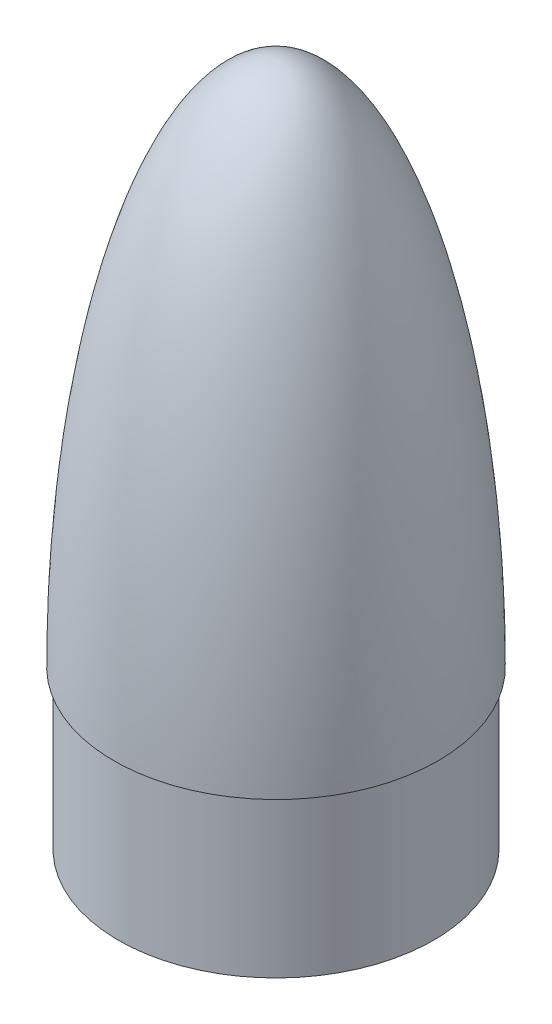
SolidWorks part; units mm, degrees
material "ABS"
ref_plane "Front Plane" through (0, 0, 0) normal (0, 0, 1) x (1, 0, 0)
ref_plane "Top Plane" through (0, 0, 0) normal (0, 1, 0) x (1, 0, 0)
ref_plane "Right Plane" through (0, 0, 0) normal (1, 0, 0) x (0, 0, -1)
sketch "Sketch1" plane through (0, 0, 0) normal (0, 0, 1) x (1, 0, 0)
  line L0 (0, 254) -> (0, 0) construction
  line L1 (78.359, 0) -> (0, 0)
  line L2 (0, 0) -> (0, 254)
  spline S0 degree 4 poles (77.9662, -25.3999) (78.0154, -23.8095) (78.1056, -20.6522) (78.1976, -16.6458) (78.2773, -11.9379) (78.3233, -7.8867) (78.3478, -4.9036) (78.3593, -1.4843) (78.3601, 0.7911) (78.3527, 3.5863) (78.3388, 5.9889) (78.318, 8.3522) (78.2903, 10.7456) (78.247, 13.7314) (78.1811, 17.3117) (78.0839, 21.4904) (77.9448, 26.2641) (77.7777, 31.0376) (77.5823, 35.8096) (77.3585, 40.5805) (77.0429, 46.5423) (76.6791, 52.5014) (76.2664, 58.4574) (75.8041, 64.4096) (75.404, 69.1689) (74.8656, 75.1148) (74.1574, 82.244) (73.2383, 90.5517) (72.0557, 100.0308) (70.7355, 109.4917) (69.2709, 118.9313) (67.25, 130.6999) (64.5017, 144.7638) (61.3086, 158.736) (57.591, 172.5772) (53.383, 186.2759) (49.2387, 198.0448) (44.4832, 209.5873) (38.9429, 220.7192) (34.2562, 228.6936) (29.8187, 235.0954) (25.6242, 240.1829) (21.9789, 243.9262) (18.5702, 246.8595) (15.4743, 249.0762) (12.5634, 250.7857) (9.7723, 252.0835) (7.0631, 253.0286) (4.2754, 253.6868) (2.188, 253.9399) (0.7672, 253.9999) (0, 254) knots 0 0 0 0 0 0.020823 0.041645 0.052056 0.062468 0.072879 0.08329 0.09112 0.098949 0.106779 0.114608 0.122438 0.130267 0.145926 0.161585 0.177244 0.192903 0.208562 0.224221 0.23988 0.271198 0.286857 0.302516 0.318175 0.333834 0.365152 0.39647 0.427788 0.459106 0.490424 0.521742 0.584379 0.647015 0.678333 0.709651 0.772287 0.810589 0.841907 0.872608 0.893486 0.912628 0.928287 0.941045 0.952387 0.962498 0.972496 0.981349 0.98995 1 1 1 1 1 construction
  spline S1 degree 4 poles (78.359, 0) (78.359, 0.5473) (78.3578, 1.6496) (78.3527, 3.5863) (78.3388, 5.9889) (78.318, 8.3522) (78.2903, 10.7456) (78.247, 13.7314) (78.1811, 17.3117) (78.0839, 21.4904) (77.9448, 26.2641) (77.7777, 31.0376) (77.5823, 35.8096) (77.3585, 40.5805) (77.0429, 46.5423) (76.6791, 52.5014) (76.2664, 58.4574) (75.8041, 64.4096) (75.404, 69.1689) (74.8656, 75.1148) (74.1574, 82.244) (73.2383, 90.5517) (72.0557, 100.0308) (70.7355, 109.4917) (69.2709, 118.9313) (67.25, 130.6999) (64.5017, 144.7638) (61.3086, 158.736) (57.591, 172.5772) (53.383, 186.2759) (49.2387, 198.0448) (44.4832, 209.5873) (38.9429, 220.7192) (34.2562, 228.6936) (29.8187, 235.0954) (25.6242, 240.1829) (21.9789, 243.9262) (18.5702, 246.8595) (15.4743, 249.0762) (12.5634, 250.7857) (9.7723, 252.0835) (7.0631, 253.0286) (4.2754, 253.6868) (2.188, 253.9399) (0.7672, 253.9999) (0, 254) knots 0.08329 0.08329 0.08329 0.08329 0.08329 0.09112 0.098949 0.106779 0.114608 0.122438 0.130267 0.145926 0.161585 0.177244 0.192903 0.208562 0.224221 0.23988 0.271198 0.286857 0.302516 0.318175 0.333834 0.365152 0.39647 0.427788 0.459106 0.490424 0.521742 0.584379 0.647015 0.678333 0.709651 0.772287 0.810589 0.841907 0.872608 0.893486 0.912628 0.928287 0.941045 0.952387 0.962498 0.972496 0.981349 0.98995 1 1 1 1 1
revolve "Revolve1" add sketch "Sketch1" angle 360 about L0
sketch "Sketch2" plane through (0, 0, 0) normal (0, -1, 0) x (1, 0, 0)
  circle A0 centre (0, 0) radius 76.2
extrude "Boss-Extrude1" add sketch "Sketch2" along normal blind 76.2
ref_axis "Axis1" through (0, 270.51, 0) along (0, -1, 0)
sketch "Sketch4" plane through (0, 0, 0) normal (0, 1, 0) x (1, 0, 0)
  line L0 (76.2, 0) -> (-78.359, 0) construction
  line L1 (0, -78.359) -> (0, 90.3851) construction
  circle A0 centre (0, 0) radius 76.2 construction
  circle A1 centre (0, 0) radius 78.359 construction
  circle A2 centre (48.26, 0) radius 17.78
  circle A3 centre (0, -48.26) radius 17.78
  circle A4 centre (-48.26, 0) radius 17.78
  circle A5 centre (0, 48.26) radius 17.78
  point P20 (0, 0)
  point P43 (0, 0.8087)
  dimension "D2" = 35.56
  dimension "D1" = 48.26
  dimension "D3" = 4
extrude "Cut-Extrude1" cut sketch "Sketch4" along normal blind 96.52
sketch "Sketch5" plane through (0, 0, 0) normal (0, 1, 0) x (1, 0, 0)
  line L0 (-83.8326, 0) -> (109.4642, 0) construction
  line L1 (0, 82.5318) -> (0, -82.1463) construction
  circle A0 centre (20.32, 0) radius 8.255
  circle A1 centre (10.16, -17.5976) radius 8.255
  circle A2 centre (-10.16, -17.5976) radius 8.255
  circle A3 centre (-20.32, 0) radius 8.255
  circle A4 centre (-10.16, 17.5976) radius 8.255
  circle A5 centre (10.16, 17.5976) radius 8.255
  point P20 (0, 0)
  dimension "D2" = 16.51
  dimension "D1" = 20.32
  dimension "D3" = 6
extrude "Cut-Extrude2" cut sketch "Sketch5" along normal blind 119.38 from offset 106.68
sketch "Sketch6" plane through (0, 0, 0) normal (0, 0, 1) x (1, 0, 0)
  line L0 (-30.48, 96.52) -> (-48.26, 117.7094)
  line L1 (-48.26, 96.52) -> (-48.26, 0) construction
  line L2 (-66.04, 96.52) -> (-30.48, 96.52) construction
  line L3 (-48.26, 117.7094) -> (-48.26, 96.52)
  line L4 (-48.26, 96.52) -> (-30.48, 96.52)
  dimension "D1" = 50
revolve "Cut-Revolve2" cut sketch "Sketch6" angle 360 about axis through (-48.26, 96.52, 0) along (0, -1, 0)
sketch "Sketch7" plane through (0, 0, 0) normal (0, 0, 1) x (1, 0, 0)
  line L0 (17.78, 96.52) -> (0, 117.7094)
  line L1 (0, 270.51) -> (0, -92.71) construction
  line L2 (-17.78, 96.52) -> (17.78, 96.52) construction
  line L3 (0, 117.7094) -> (0, 96.52)
  line L4 (0, 96.52) -> (17.78, 96.52)
  dimension "D1" = 50
ref_plane "Plane1" through (0, 0, 48.26) normal (0, 0, 1) x (1, 0, 0)
sketch "Sketch8" plane through (0, 0, 48.26) normal (0, 0, 1) x (1, 0, 0)
  line L0 (0, 96.52) -> (17.78, 96.52)
  line L1 (17.78, 96.52) -> (0, 117.7094)
  line L2 (0, 117.7094) -> (0, 96.52)
revolve "Cut-Revolve4" cut sketch "Sketch8" angle 360 about axis through (0, 96.52, 48.26) along (0, -1, 0)
sketch "Sketch9" plane through (0, 0, 0) normal (0, 0, 1) x (1, 0, 0)
  line L0 (48.26, 96.52) -> (66.04, 96.52)
  line L1 (30.48, 96.52) -> (66.04, 96.52) construction
  line L2 (66.04, 96.52) -> (48.26, 117.7094)
  line L3 (48.26, 96.52) -> (48.26, 0) construction
  line L4 (48.26, 117.7094) -> (48.26, 96.52)
  dimension "D1" = 50
revolve "Cut-Revolve5" cut sketch "Sketch9" angle 360 about axis through (48.26, 96.52, 0) along (0, -1, 0)
ref_plane "Plane2" through (0, 0, -48.26) normal (0, 0, 1) x (1, 0, 0)
sketch "Sketch11" plane through (0, 0, -48.26) normal (0, 0, 1) x (1, 0, 0)
  line L0 (0, 96.52) -> (17.78, 96.52)
  line L1 (17.78, 96.52) -> (-17.78, 96.52) construction
  line L2 (17.78, 96.52) -> (0, 117.7094)
  line L3 (0, 117.7094) -> (0, 96.52)
revolve "Cut-Revolve6" cut sketch "Sketch11" angle 360 about axis through (0, 96.52, -48.26) along (0, -1, 0)
sketch "Sketch12" plane through (0, 0, 0) normal (0, 0, 1) x (1, 0, 0)
  line L0 (-20.32, 226.06) -> (-12.065, 226.06)
  line L1 (-28.575, 226.06) -> (-12.065, 226.06) construction
  line L2 (-12.065, 226.06) -> (-20.32, 235.8979)
  line L3 (-20.32, 226.06) -> (-20.32, 106.68) construction
  line L4 (-20.32, 235.8979) -> (-20.32, 226.06)
  dimension "D1" = 50
revolve "Cut-Revolve7" cut sketch "Sketch12" angle 360 about axis through (-20.32, 226.06, 0) along (0, -1, 0)
sketch "Sketch14" plane through (0, 0, 0) normal (0, 0, 1) x (1, 0, 0)
  line L0 (20.32, 226.06) -> (28.575, 226.06)
  line L1 (12.065, 226.06) -> (28.575, 226.06) construction
  line L2 (28.575, 226.06) -> (20.32, 235.8979)
  line L3 (20.32, 226.06) -> (20.32, 106.68) construction
  line L4 (20.32, 235.8979) -> (20.32, 226.06)
  dimension "D1" = 50
revolve "Cut-Revolve8" cut sketch "Sketch14" angle 360 about L4
ref_plane "Plane3" through (0, 0, 17.5976) normal (0, 0, 1) x (1, 0, 0)
sketch "Sketch15" plane through (0, 0, 17.5976) normal (0, 0, 1) x (1, 0, 0)
  line L0 (-10.16, 226.06) -> (-1.905, 226.06)
  line L1 (-18.415, 226.06) -> (-1.905, 226.06) construction
  line L2 (-1.905, 226.06) -> (-10.16, 235.8979)
  line L3 (-10.16, 226.06) -> (-10.16, 106.68) construction
  line L4 (-10.16, 235.8979) -> (-10.16, 226.06)
  dimension "D1" = 50
revolve "Cut-Revolve9" cut sketch "Sketch15" angle 360 about axis through (-10.16, 226.06, 17.5976) along (0, -1, 0)
sketch "Sketch16" plane through (0, 0, 17.5976) normal (0, 0, 1) x (1, 0, 0)
  line L0 (10.16, 226.06) -> (18.415, 226.06)
  line L1 (1.905, 226.06) -> (18.415, 226.06) construction
  line L2 (18.415, 226.06) -> (10.16, 235.8979)
  line L3 (10.16, 226.06) -> (10.16, 106.68) construction
  line L4 (10.16, 235.8979) -> (10.16, 226.06)
  dimension "D1" = 50
revolve "Cut-Revolve10" cut sketch "Sketch16" angle 360 about L4
ref_plane "Plane4" through (0, 0, -17.5976) normal (0, 0, 1) x (1, 0, 0)
sketch "Sketch17" plane through (0, 0, -17.5976) normal (0, 0, 1) x (1, 0, 0)
  line L0 (10.16, 226.06) -> (18.415, 226.06)
  line L1 (18.415, 226.06) -> (1.905, 226.06) construction
  line L2 (18.415, 226.06) -> (10.16, 235.8979)
  line L3 (10.16, 235.8979) -> (10.16, 226.06)
revolve "Cut-Revolve11" cut sketch "Sketch17" angle 360 about L3
sketch "Sketch18" plane through (0, 0, -17.5976) normal (0, 0, 1) x (1, 0, 0)
  line L0 (-10.16, 226.06) -> (-1.905, 226.06)
  line L1 (-1.905, 226.06) -> (-18.415, 226.06) construction
  line L2 (-1.905, 226.06) -> (-10.16, 235.8979)
  line L3 (-10.16, 235.8979) -> (-10.16, 226.06)
revolve "Cut-Revolve12" cut sketch "Sketch18" angle 360 about L3
sketch "Sketch19" plane through (0, 0, 0) normal (0, 1, 0) x (1, 0, 0)
  circle A0 centre (0, 0) radius 15.24
  dimension "D1" = 30.48
extrude "Cut-Extrude3" cut sketch "Sketch19" along normal blind 101.6 from offset 25.4 offset against normal yes
sketch "Sketch20" plane through (0, 0, 0) normal (0, 0, 1) x (1, 0, 0)
  line L5 (0, 76.2) -> (15.24, 76.2)
  line L6 (-15.24, 76.2) -> (15.24, 76.2) construction
  line L7 (15.24, 76.2) -> (0, 94.3623)
  line L8 (0, 270.51) -> (0, -92.71) construction
  line L9 (0, 94.3623) -> (0, 76.2)
  dimension "D1" = 50
revolve "Cut-Revolve13" cut sketch "Sketch20" angle 360 about axis through (0, 270.51, 0) along (0, -1, 0)
sketch "Sketch21" plane through (0, -76.2, 0) normal (0, -1, 0) x (1, 0, 0)
  line L1 (-31.75, 31.75) -> (31.75, 31.75) construction
  line L2 (-31.75, 31.75) -> (-31.75, -31.75) construction
  line L3 (-31.75, -31.75) -> (31.75, -31.75) construction
  line L4 (31.75, 31.75) -> (31.75, -31.75) construction
  circle A0 centre (-44.163, 0) radius 2.54
  circle A1 centre (0, 44.163) radius 2.54
  circle A2 centre (44.163, 0) radius 2.54
  circle A3 centre (0, -44.163) radius 2.54
  point P12 (-31.75, 0)
  dimension "D1" = 63.5
  dimension "D3" = 5.08
  dimension "D5" = 12.413
  dimension "D8" = 5.08
  dimension "D9" = 5.08
  dimension "D10" = 5.08
  dimension "D2" = 63.5
  dimension "D4" = 12.413
  dimension "D6" = 12.413
  dimension "D7" = 12.413
extrude "Cut-Extrude4" cut sketch "Sketch21" against normal blind 6.35
sketch "Sketch22" plane through (0, -76.2, 0) normal (0, -1, 0) x (1, 0, 0)
  line L0 (-71.842, 0) -> (0, 71.842) construction
  line L1 (0, 71.842) -> (71.842, 0) construction
  line L2 (71.842, 0) -> (0, -71.842) construction
  line L3 (0, -71.842) -> (-71.842, 0) construction
  line L4 (0, -44.163) -> (44.163, 0) construction
  circle A0 centre (-35.921, -35.921) radius 3
  circle A1 centre (-35.921, 35.921) radius 3
  circle A2 centre (35.921, 35.921) radius 3
  circle A3 centre (35.921, -35.921) radius 3
  dimension "D6" = 6
  dimension "D7" = 6
  dimension "D8" = 6
  dimension "D9" = 6
  dimension "D1" = 101.6
  dimension "D2" = 101.6
  dimension "D3" = 50.8
  dimension "D4" = 50.8
  dimension "D5" = 90
extrude "Cut-Extrude5" cut sketch "Sketch22" against normal blind 12.7
sketch "Sketch3" plane through (0, 0, 0) normal (0, 0, 1) x (1, 0, 0)
  line L0 (0, 0) -> (50.6956, 0)
  line L1 (-76.2, 0) -> (76.2, 0) construction
  line L2 (0, 0) -> (0, 122.511)
  line L3 (0, 270.51) -> (0, -92.71) construction
  arc A0 (50.6956, 0) -> (0, 122.511) centre (-122.6821, 0) ccw
revolve "Cut-Revolve1" cut sketch "Sketch3" angle 360 about axis through (0, 270.51, 0) along (0, -1, 0)
equation "\"Bodytube_OD\" = 6.17in"
equation "\"Bodytube_ID\" = 5.998in"
equation "\"R\"= \"Bodytube_ID\" / 2"
equation "\"L\"= 30in"
